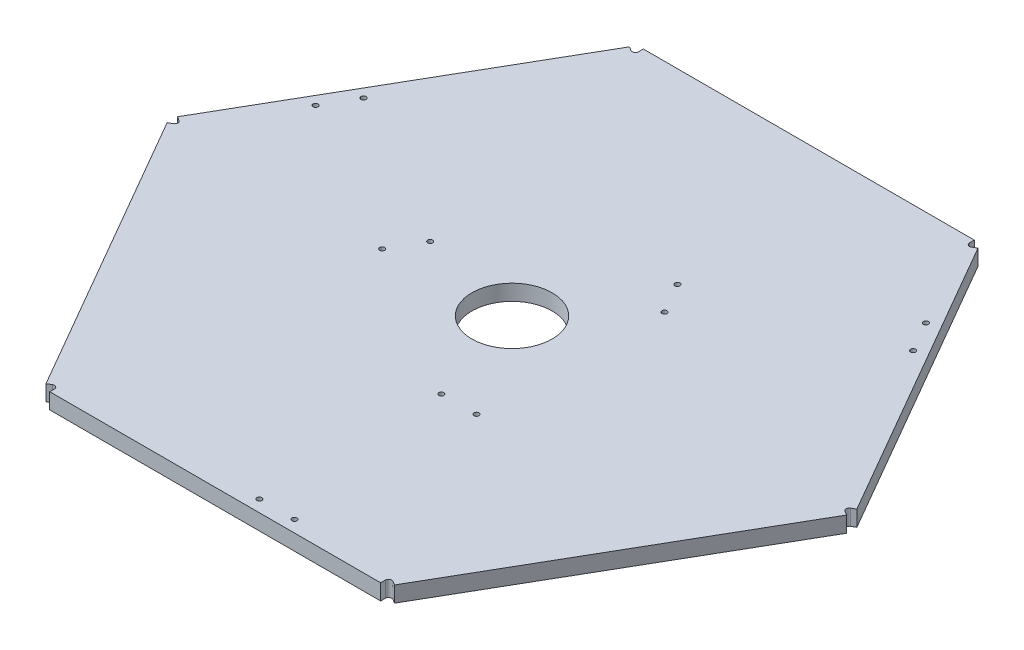
SolidWorks part; units mm, degrees
ref_plane "Front Plane" through (0, 0, 0) normal (0, 0, 1) x (1, 0, 0)
ref_plane "Top Plane" through (0, 0, 0) normal (0, 1, 0) x (1, 0, 0)
ref_plane "Right Plane" through (0, 0, 0) normal (1, 0, 0) x (0, 0, -1)
sketch "Sketch1" plane through (0, 0, 0) normal (0, 1, 0) x (1, 0, 0)
  line L1 (54.2709, 94) -> (-54.2709, 94)
  line L2 (-54.2709, 94) -> (-108.5419, 0)
  line L3 (-108.5419, 0) -> (-54.2709, -94)
  line L4 (-54.2709, -94) -> (54.2709, -94)
  line L5 (54.2709, -94) -> (108.5419, 0)
  line L6 (108.5419, 0) -> (54.2709, 94)
  circle A0 centre (0, 0) radius 94 construction
  dimension "D1" = 188
extrude "Boss-Extrude1" add sketch "Sketch1" along normal blind 5
sketch "Sketch7" plane through (0, 5, 0) normal (0, 1, 0) x (1, 0, 0)
  line L0 (54.2709, 94) -> (-54.2709, 94) construction
  line L1 (53.4049, 92.5) -> (-53.4049, 92.5) construction
  line L2 (-53.4049, 92.5) -> (-106.8098, 0) construction
  line L3 (-106.8098, 0) -> (-53.4049, -92.5) construction
  line L4 (-53.4049, -92.5) -> (53.4049, -92.5) construction
  line L5 (53.4049, -92.5) -> (106.8098, 0) construction
  line L6 (106.8098, 0) -> (53.4049, 92.5) construction
  circle A0 centre (0, 0) radius 92.5 construction
  circle A1 centre (-53.4049, 92.5) radius 1
  dimension "D2" = 2
  dimension "D1" = 185
extrude "Cut-Extrude5" cut sketch "Sketch7" against normal through all
sketch "Sketch9" plane through (0, 5, 0) normal (0, 1, 0) x (1, 0, 0)
  circle A0 centre (0, 0) radius 12.7
  dimension "D1" = 25.4
extrude "Cut-Extrude6" cut sketch "Sketch9" against normal up to next
sketch "Sketch13" plane through (0, 5, 0) normal (0, 1, 0) x (1, 0, 0)
  circle A0 centre (-88.84, 26.6245) radius 0.8
  circle A1 centre (-38.9353, -2.188) radius 0.8
  circle A2 centre (67.4775, 63.6255) radius 0.8
  circle A3 centre (21.3625, -90.25) radius 0.8
  circle A4 centre (-83.2775, 36.2591) radius 0.8
  circle A22 centre (-33.3728, 7.4466) radius 0.8
  circle A24 centre (73.04, 53.9909) radius 0.8
  circle A26 centre (17.5728, 34.813) radius 0.8
  circle A28 centre (23.1353, 25.1784) radius 0.8
  circle A38 centre (10.2375, -90.25) radius 0.8
  circle A40 centre (21.3625, -32.625) radius 0.8
  circle A42 centre (10.2375, -32.625) radius 0.8
  dimension "D1" = 1.6
extrude "Cut-Extrude7" cut sketch "Sketch13" against normal through all
sketch "Sketch17" plane through (0, 5, 0) normal (0, 1, 0) x (1, 0, 0)
  line L0 (-52.4049, 92.5) -> (-52.4049, 94)
  line L1 (54.2709, 94) -> (-54.2709, 94) construction
  line L2 (-52.4049, 94) -> (-54.2709, 94)
  line L3 (-55.2039, 92.384) -> (-53.9049, 91.634)
  line L4 (-54.2709, 94) -> (-108.5419, 0) construction
  line L5 (-55.2039, 92.384) -> (-54.2709, 94)
  circle A0 centre (-53.4049, 92.5) radius 1 construction
  arc A1 (-53.9049, 91.634) -> (-52.4049, 92.5) centre (-53.4049, 92.5) ccw
extrude "Cut-Extrude8" cut sketch "Sketch17" against normal through all
pattern_circular "CirPattern1" count 6 over 360 about axis through (0, 5, 0) along (0, 1, 0) of "Cut-Extrude5", "Cut-Extrude8"
